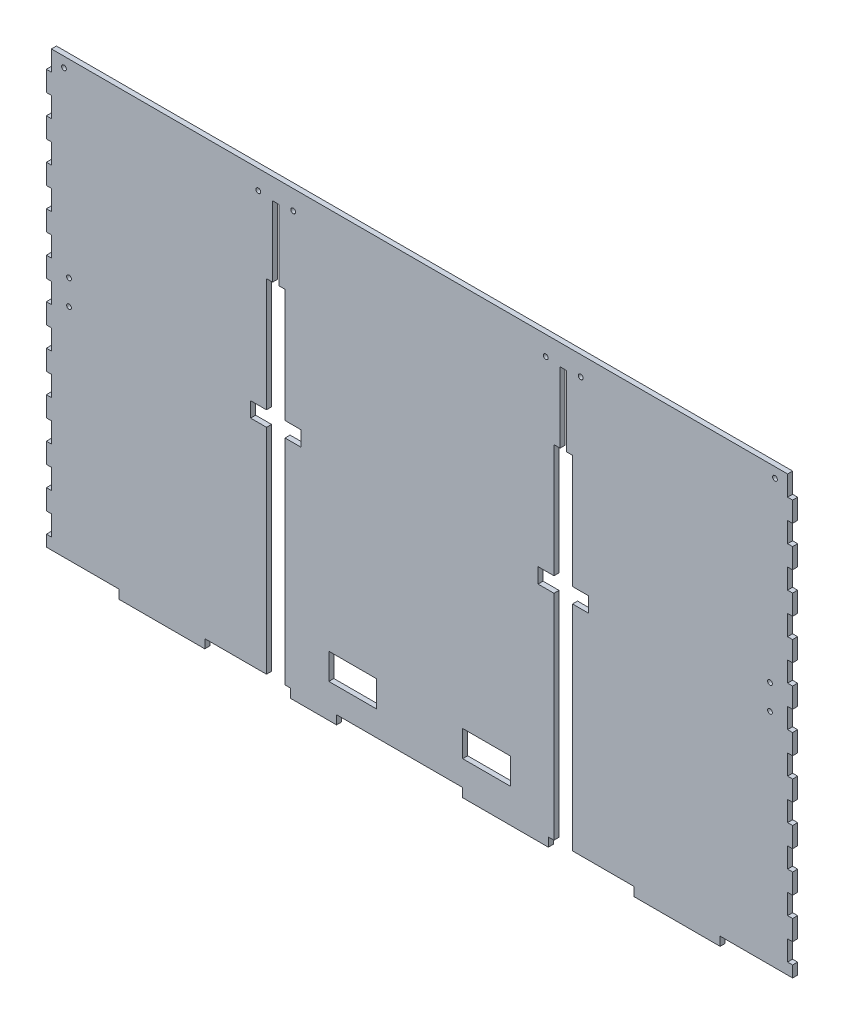
SolidWorks part; units mm, degrees
other "Markup1"
sketch "Sketch18" plane through (-235.3945, -139.7, 3.175) normal (0, 0, 1) x (1, 0, 0)
material "Acrylic (Medium-high impact)"
ref_plane "Front Plane" through (0, 0, 0) normal (0, 0, 1) x (1, 0, 0)
ref_plane "Top Plane" through (0, 0, 0) normal (0, 1, 0) x (1, 0, 0)
ref_plane "Right Plane" through (0, 0, 0) normal (1, 0, 0) x (0, 0, -1)
sketch "Sketch1" plane through (0, 0, 0) normal (0, 0, 1) x (1, 0, 0)
  line L0 (0, 139.7) -> (0, -139.7) construction
  line L1 (-406.4, 139.7) -> (406.4, 139.7)
  line L2 (-406.4, 139.7) -> (-406.4, -139.7)
  line L3 (-406.4, -139.7) -> (406.4, -139.7)
  line L4 (406.4, 139.7) -> (406.4, -139.7)
  line L49 (-381, 127) -> (-381, 114.3)
  line L54 (-381, 139.7) -> (-377.825, 139.7)
  line L55 (-381, 139.7) -> (-381, 127)
  line L56 (-381, 127) -> (-377.825, 127)
  line L57 (-377.825, 139.7) -> (-377.825, 127)
  line L58 (-381, 127) -> (-377.825, 127)
  line L59 (-377.825, 127) -> (-377.825, 114.3)
  line L60 (-381, 114.3) -> (-377.825, 114.3)
  line L61 (-381, 114.3) -> (-381, 101.6)
  line L62 (-381, 114.3) -> (-377.825, 114.3)
  line L63 (-377.825, 114.3) -> (-377.825, 101.6)
  line L64 (-381, 101.6) -> (-377.825, 101.6)
  line L65 (-381, 101.6) -> (-381, 88.9)
  line L66 (-381, 101.6) -> (-377.825, 101.6)
  line L67 (-377.825, 101.6) -> (-377.825, 88.9)
  line L68 (-381, 88.9) -> (-377.825, 88.9)
  line L69 (-381, 88.9) -> (-381, 76.2)
  line L70 (-381, 88.9) -> (-377.825, 88.9)
  line L71 (-377.825, 88.9) -> (-377.825, 76.2)
  line L72 (-381, 76.2) -> (-377.825, 76.2)
  line L73 (-381, 76.2) -> (-381, 63.5)
  line L74 (-381, 76.2) -> (-377.825, 76.2)
  line L75 (-377.825, 76.2) -> (-377.825, 63.5)
  line L76 (-381, 63.5) -> (-377.825, 63.5)
  line L77 (-381, 63.5) -> (-381, 50.8)
  line L78 (-381, 63.5) -> (-377.825, 63.5)
  line L79 (-377.825, 63.5) -> (-377.825, 50.8)
  line L80 (-381, 50.8) -> (-377.825, 50.8)
  line L81 (-381, 50.8) -> (-381, 38.1)
  line L82 (-381, 50.8) -> (-377.825, 50.8)
  line L83 (-377.825, 50.8) -> (-377.825, 38.1)
  line L84 (-381, 38.1) -> (-377.825, 38.1)
  line L85 (-381, 38.1) -> (-381, 25.4)
  line L86 (-381, 38.1) -> (-377.825, 38.1)
  line L87 (-377.825, 38.1) -> (-377.825, 25.4)
  line L88 (-381, 25.4) -> (-377.825, 25.4)
  line L89 (377.825, 127) -> (377.825, 114.3)
  line L90 (377.825, 139.7) -> (381, 139.7)
  line L91 (377.825, 139.7) -> (377.825, 127)
  line L92 (377.825, 127) -> (381, 127)
  line L93 (381, 139.7) -> (381, 127)
  line L94 (377.825, 127) -> (381, 127)
  line L95 (381, 127) -> (381, 114.3)
  line L96 (377.825, 114.3) -> (381, 114.3)
  line L97 (377.825, 114.3) -> (377.825, 101.6)
  line L98 (377.825, 114.3) -> (381, 114.3)
  line L99 (381, 114.3) -> (381, 101.6)
  line L100 (377.825, 101.6) -> (381, 101.6)
  line L101 (377.825, 101.6) -> (377.825, 88.9)
  line L102 (377.825, 101.6) -> (381, 101.6)
  line L103 (381, 101.6) -> (381, 88.9)
  line L104 (377.825, 88.9) -> (381, 88.9)
  line L105 (377.825, 88.9) -> (377.825, 76.2)
  line L106 (377.825, 88.9) -> (381, 88.9)
  line L107 (381, 88.9) -> (381, 76.2)
  line L108 (377.825, 76.2) -> (381, 76.2)
  line L109 (377.825, 76.2) -> (377.825, 63.5)
  line L110 (377.825, 76.2) -> (381, 76.2)
  line L111 (381, 76.2) -> (381, 63.5)
  line L112 (377.825, 63.5) -> (381, 63.5)
  line L113 (377.825, 63.5) -> (377.825, 50.8)
  line L114 (377.825, 63.5) -> (381, 63.5)
  line L115 (381, 63.5) -> (381, 50.8)
  line L116 (377.825, 50.8) -> (381, 50.8)
  line L117 (377.825, 50.8) -> (377.825, 38.1)
  line L118 (377.825, 50.8) -> (381, 50.8)
  line L119 (381, 50.8) -> (381, 38.1)
  line L120 (377.825, 38.1) -> (381, 38.1)
  line L121 (377.825, 38.1) -> (377.825, 25.4)
  line L122 (377.825, 38.1) -> (381, 38.1)
  line L123 (381, 38.1) -> (381, 25.4)
  line L124 (377.825, 25.4) -> (381, 25.4)
  line L125 (-352.2133, -134.112) -> (-352.2133, -139.7)
  line L126 (-406.4, -134.112) -> (-352.2133, -134.112)
  line L127 (-406.4, -134.112) -> (-406.4, -139.7)
  line L128 (-406.4, -139.7) -> (-352.2133, -139.7)
  line L129 (-352.2133, -134.112) -> (-352.2133, -139.7)
  line L130 (-352.2133, -134.112) -> (-298.0267, -134.112)
  line L131 (-298.0267, -134.112) -> (-298.0267, -139.7)
  line L132 (-352.2133, -139.7) -> (-298.0267, -139.7)
  line L133 (-298.0267, -134.112) -> (-298.0267, -139.7)
  line L134 (-298.0267, -134.112) -> (-243.84, -134.112)
  line L135 (-243.84, -134.112) -> (-243.84, -139.7)
  line L136 (-298.0267, -139.7) -> (-243.84, -139.7)
  line L137 (-243.84, -134.112) -> (-243.84, -139.7)
  line L138 (-243.84, -134.112) -> (-189.6533, -134.112)
  line L139 (-189.6533, -134.112) -> (-189.6533, -139.7)
  line L140 (-243.84, -139.7) -> (-189.6533, -139.7)
  line L141 (-189.6533, -134.112) -> (-189.6533, -139.7)
  line L142 (-189.6533, -134.112) -> (-135.4667, -134.112)
  line L143 (-135.4667, -134.112) -> (-135.4667, -139.7)
  line L144 (-189.6533, -139.7) -> (-135.4667, -139.7)
  line L145 (-135.4667, -134.112) -> (-135.4667, -139.7)
  line L146 (-135.4667, -134.112) -> (-81.28, -134.112)
  line L147 (-81.28, -134.112) -> (-81.28, -139.7)
  line L148 (-135.4667, -139.7) -> (-81.28, -139.7)
  line L149 (-81.28, -134.112) -> (-81.28, -139.7)
  line L150 (-81.28, -134.112) -> (-27.0933, -134.112)
  line L151 (-27.0933, -134.112) -> (-27.0933, -139.7)
  line L152 (-81.28, -139.7) -> (-27.0933, -139.7)
  line L153 (-27.0933, -134.112) -> (-27.0933, -139.7)
  line L154 (-27.0933, -134.112) -> (27.0933, -134.112)
  line L155 (27.0933, -134.112) -> (27.0933, -139.7)
  line L156 (-27.0933, -139.7) -> (27.0933, -139.7)
  line L157 (27.0933, -134.112) -> (27.0933, -139.7)
  line L158 (27.0933, -134.112) -> (81.28, -134.112)
  line L159 (81.28, -134.112) -> (81.28, -139.7)
  line L160 (27.0933, -139.7) -> (81.28, -139.7)
  line L161 (81.28, -134.112) -> (81.28, -139.7)
  line L162 (81.28, -134.112) -> (135.4667, -134.112)
  line L163 (135.4667, -134.112) -> (135.4667, -139.7)
  line L164 (81.28, -139.7) -> (135.4667, -139.7)
  line L165 (135.4667, -134.112) -> (135.4667, -139.7)
  line L166 (135.4667, -134.112) -> (189.6533, -134.112)
  line L167 (189.6533, -134.112) -> (189.6533, -139.7)
  line L168 (135.4667, -139.7) -> (189.6533, -139.7)
  line L169 (189.6533, -134.112) -> (189.6533, -139.7)
  line L170 (189.6533, -134.112) -> (243.84, -134.112)
  line L171 (243.84, -134.112) -> (243.84, -139.7)
  line L172 (189.6533, -139.7) -> (243.84, -139.7)
  line L173 (243.84, -134.112) -> (243.84, -139.7)
  line L174 (243.84, -134.112) -> (298.0267, -134.112)
  line L175 (298.0267, -134.112) -> (298.0267, -139.7)
  line L176 (243.84, -139.7) -> (298.0267, -139.7)
  line L177 (298.0267, -134.112) -> (298.0267, -139.7)
  line L178 (298.0267, -134.112) -> (352.2133, -134.112)
  line L179 (352.2133, -134.112) -> (352.2133, -139.7)
  line L180 (298.0267, -139.7) -> (352.2133, -139.7)
  line L181 (352.2133, -134.112) -> (352.2133, -139.7)
  line L182 (352.2133, -134.112) -> (406.4, -134.112)
  line L183 (406.4, -134.112) -> (406.4, -139.7)
  line L184 (352.2133, -139.7) -> (406.4, -139.7)
  line L205 (-90.678, 84.5227) -> (-90.678, -139.7) construction
  line L206 (90.678, 84.5227) -> (90.678, -139.7) construction
  line L207 (-90.678, -27.5886) -> (90.678, -27.5886) construction
  line L208 (-381, 25.4) -> (-381, 12.7)
  line L209 (-381, 25.4) -> (-377.825, 25.4)
  line L210 (-377.825, 25.4) -> (-377.825, 12.7)
  line L211 (-381, 12.7) -> (-377.825, 12.7)
  line L212 (-381, 12.7) -> (-381, 0)
  line L213 (-381, 12.7) -> (-377.825, 12.7)
  line L214 (-377.825, 12.7) -> (-377.825, 0)
  line L215 (-381, 0) -> (-377.825, 0)
  line L224 (-377.825, 0) -> (377.825, 0) construction
  line L229 (377.825, 25.4) -> (377.825, 12.7)
  line L230 (377.825, 25.4) -> (381, 25.4)
  line L231 (381, 25.4) -> (381, 12.7)
  line L232 (377.825, 12.7) -> (381, 12.7)
  line L233 (377.825, 12.7) -> (377.825, 0)
  line L234 (377.825, 12.7) -> (381, 12.7)
  line L235 (381, 12.7) -> (381, 0)
  line L236 (377.825, 0) -> (381, 0)
  line L237 (-381, 0) -> (-381, -12.7)
  line L238 (-381, 0) -> (-377.825, 0)
  line L239 (-377.825, 0) -> (-377.825, -12.7)
  line L240 (-381, -12.7) -> (-377.825, -12.7)
  line L241 (-381, -12.7) -> (-381, -25.4)
  line L242 (-381, -12.7) -> (-377.825, -12.7)
  line L243 (-377.825, -12.7) -> (-377.825, -25.4)
  line L244 (-381, -25.4) -> (-377.825, -25.4)
  line L245 (-381, -25.4) -> (-381, -38.1)
  line L246 (-381, -25.4) -> (-377.825, -25.4)
  line L247 (-377.825, -25.4) -> (-377.825, -38.1)
  line L248 (-381, -38.1) -> (-377.825, -38.1)
  line L249 (-381, -38.1) -> (-381, -50.8)
  line L250 (-381, -38.1) -> (-377.825, -38.1)
  line L251 (-377.825, -38.1) -> (-377.825, -50.8)
  line L252 (-381, -50.8) -> (-377.825, -50.8)
  line L253 (-381, -50.8) -> (-381, -63.5)
  line L254 (-381, -50.8) -> (-377.825, -50.8)
  line L255 (-377.825, -50.8) -> (-377.825, -63.5)
  line L256 (-381, -63.5) -> (-377.825, -63.5)
  line L257 (-381, -63.5) -> (-381, -76.2)
  line L258 (-381, -63.5) -> (-377.825, -63.5)
  line L259 (-377.825, -63.5) -> (-377.825, -76.2)
  line L260 (-381, -76.2) -> (-377.825, -76.2)
  line L261 (-381, -76.2) -> (-381, -88.9)
  line L262 (-381, -76.2) -> (-377.825, -76.2)
  line L263 (-377.825, -76.2) -> (-377.825, -88.9)
  line L264 (-381, -88.9) -> (-377.825, -88.9)
  line L265 (-381, -88.9) -> (-381, -101.6)
  line L266 (-381, -88.9) -> (-377.825, -88.9)
  line L267 (-377.825, -88.9) -> (-377.825, -101.6)
  line L268 (-381, -101.6) -> (-377.825, -101.6)
  line L269 (-381, -101.6) -> (-381, -114.3)
  line L270 (-381, -101.6) -> (-377.825, -101.6)
  line L271 (-377.825, -101.6) -> (-377.825, -114.3)
  line L272 (-381, -114.3) -> (-377.825, -114.3)
  line L273 (-381, -114.3) -> (-381, -127)
  line L274 (-381, -114.3) -> (-377.825, -114.3)
  line L275 (-377.825, -114.3) -> (-377.825, -127)
  line L276 (-381, -127) -> (-377.825, -127)
  line L277 (-381, -127) -> (-381, -139.7)
  line L278 (-381, -127) -> (-377.825, -127)
  line L279 (-377.825, -127) -> (-377.825, -139.7)
  line L280 (-381, -139.7) -> (-377.825, -139.7)
  line L281 (377.825, 0) -> (377.825, -12.7)
  line L282 (377.825, 0) -> (381, 0)
  line L283 (381, 0) -> (381, -12.7)
  line L284 (377.825, -12.7) -> (381, -12.7)
  line L285 (377.825, -12.7) -> (377.825, -25.4)
  line L286 (377.825, -12.7) -> (381, -12.7)
  line L287 (381, -12.7) -> (381, -25.4)
  line L288 (377.825, -25.4) -> (381, -25.4)
  line L289 (377.825, -25.4) -> (377.825, -38.1)
  line L290 (377.825, -25.4) -> (381, -25.4)
  line L291 (381, -25.4) -> (381, -38.1)
  line L292 (377.825, -38.1) -> (381, -38.1)
  line L293 (377.825, -38.1) -> (377.825, -50.8)
  line L294 (377.825, -38.1) -> (381, -38.1)
  line L295 (381, -38.1) -> (381, -50.8)
  line L296 (377.825, -50.8) -> (381, -50.8)
  line L297 (377.825, -50.8) -> (377.825, -63.5)
  line L298 (377.825, -50.8) -> (381, -50.8)
  line L299 (381, -50.8) -> (381, -63.5)
  line L300 (377.825, -63.5) -> (381, -63.5)
  line L301 (377.825, -63.5) -> (377.825, -76.2)
  line L302 (377.825, -63.5) -> (381, -63.5)
  line L303 (381, -63.5) -> (381, -76.2)
  line L304 (377.825, -76.2) -> (381, -76.2)
  line L305 (377.825, -76.2) -> (377.825, -88.9)
  line L306 (377.825, -76.2) -> (381, -76.2)
  line L307 (381, -76.2) -> (381, -88.9)
  line L308 (377.825, -88.9) -> (381, -88.9)
  line L309 (377.825, -88.9) -> (377.825, -101.6)
  line L310 (377.825, -88.9) -> (381, -88.9)
  line L311 (381, -88.9) -> (381, -101.6)
  line L312 (377.825, -101.6) -> (381, -101.6)
  line L313 (377.825, -101.6) -> (377.825, -114.3)
  line L314 (377.825, -101.6) -> (381, -101.6)
  line L315 (381, -101.6) -> (381, -114.3)
  line L316 (377.825, -114.3) -> (381, -114.3)
  line L317 (377.825, -114.3) -> (377.825, -127)
  line L318 (377.825, -114.3) -> (381, -114.3)
  line L319 (381, -114.3) -> (381, -127)
  line L320 (377.825, -127) -> (381, -127)
  line L321 (377.825, -127) -> (377.825, -139.7)
  line L322 (377.825, -127) -> (381, -127)
  line L323 (381, -127) -> (381, -139.7)
  line L324 (377.825, -139.7) -> (381, -139.7)
  point P6 (0, 0)
  point P128 (0, -27.5886)
  point P153 (0, 0)
  dimension "D4" = 12.7
  dimension "D5" = 3.175
  dimension "D10" = 181.356
  dimension "D12" = 755.65
  dimension "D8" = 812.8
  dimension "D11" = 54.1867
  dimension "D2" = 273.812
  dimension "D9" = 279.4
  dimension "D3" = 22
  dimension "D7" = 15
  dimension "D6" = 22
extrude "Main Extrude" add sketch "Sketch1" along normal blind 3.175 contours L321 L317 L313 L309 L305 L301 L297 L293 L289 L285 L281 L233 L229 L121 L117 L113 L109 L105 L101 L97 L89 L91 L1 L57 L59 L63 L67 L71 L75 L79 L83 L87 L210 L214 L239 L243 L247 L251 L255 L259 L263 L267 L271 L275 L279 L126 L130 L134 L138 L142 L146 | L277 L273 L269 L265 L261 L257 L253 L249 L245 L241 L237 L212 L208 L85 L81 L77 L73 L69 L65 L61 L49 L55 L1 L2 L126 | L319 L323 L182 L4 L1 L93 L95 L99 L103 L107 L111 L115 L119 L123 L231 L235 L283 L287 L291 L295 L299 L303 L307 L311 L315 | L126 L279 L3 L125 | L135 L134 L131 L3 | L143 L142 L139 L3 | L151 L150 L147 L3 | L159 L158 L155 L3 | L167 L166 L163 L3 | L175 L174 L171 L3 | L323 L182 L321 L184 | L89 L96 L95 L92 | L101 L104 L103 L100 | L109 L112 L111 L108 | L117 L120 L119 L116 | L229 L232 L231 L124 | L281 L284 L283 L236 | L289 L292 L291 L288 | L297 L300 L299 L296 | L305 L308 L307 L304 | L313 L316 L315 L312 | L323 L320 L321 L182 | L49 L60 L59 L56 | L65 L68 L67 L64 | L73 L76 L75 L72 | L81 L84 L83 L80 | L208 L211 L210 L88 | L237 L240 L239 L215 | L245 L248 L247 L244 | L253 L256 L255 L252 | L261 L264 L263 L260 | L269 L272 L271 L268 | L279 L276 L277 L126 | L277 L126 L2 L3 | L321 L182 L179 L3 | L182 L323 L3 L4 | L279 L126 L277 L128 region at (-393.7, 2.794, 0) region at (-393.7, -136.906, 0) region at (0, 2.794, 0) region at (-379.4125, 120.65, 0) region at (-379.4125, -130.556, 0) region at (-379.4125, -136.906, 0) region at (-365.0192, -136.906, 0) region at (393.7, 2.794, 0) region at (379.4125, 120.65, 0) region at (-379.4125, 95.25, 0) region at (-379.4125, -107.95, 0) region at (-270.9333, -136.906, 0) region at (393.7, -136.906, 0) region at (379.4125, 95.25, 0) region at (-379.4125, 69.85, 0) region at (-379.4125, -82.55, 0) region at (379.4125, -136.906, 0) region at (379.4125, -130.556, 0) region at (-162.56, -136.906, 0) region at (365.0192, -136.906, 0) region at (379.4125, 69.85, 0) region at (-379.4125, 44.45, 0) region at (-379.4125, -57.15, 0) region at (379.4125, -107.95, 0) region at (-54.1867, -136.906, 0) region at (270.9333, -136.906, 0) region at (379.4125, 44.45, 0) region at (-379.4125, 19.05, 0) region at (-379.4125, -31.75, 0) region at (379.4125, -82.55, 0) region at (54.1867, -136.906, 0) region at (162.56, -136.906, 0) region at (379.4125, 19.05, 0) region at (-379.4125, -6.35, 0) region at (379.4125, -57.15, 0) region at (379.4125, -6.35, 0) region at (379.4125, -31.75, 0)
sketch "Sketch8" plane through (0, 0, 3.175) normal (0, 0, 1) x (1, 0, 0)
  line L0 (-406.4, 139.7) -> (-406.4, -139.7) construction
  line L1 (-381, 28.2575) -> (-384.175, 28.2575)
  line L2 (-381, 28.2575) -> (-381, -3.6195)
  line L3 (-381, -3.6195) -> (-384.175, -3.6195)
  line L4 (-384.175, 28.2575) -> (-384.175, -3.6195)
  line L5 (-406.4, -139.7) -> (-352.2133, -139.7) construction
  line L6 (381, 28.2575) -> (384.175, 28.2575)
  line L7 (381, 28.2575) -> (381, -3.6195)
  line L8 (381, -3.6195) -> (384.175, -3.6195)
  line L9 (384.175, 28.2575) -> (384.175, -3.6195)
  line L11 (-381, 88.9) -> (-381, 76.2) construction
  line L12 (-352.2133, -134.112) -> (-298.0267, -134.112) construction
  line L13 (381, 88.9) -> (381, 76.2) construction
  line L14 (-393.7, -120.65) -> (393.7, -120.65) construction
  circle A0 centre (-393.7, -120.65) radius 1.5
  circle A1 centre (393.7, -120.65) radius 1.5
  point P6 (0, -120.65)
  point P16 (-384.175, 12.319)
  dimension "D5" = 3
  dimension "D1" = 31.877
  dimension "D2" = 3.175
  dimension "D3" = 146.431
  dimension "D4" = 19.05
  dimension "D6" = 12.7
extrude "Mount Holes" cut sketch "Sketch8" against normal through all
sketch "Sketch3" plane through (0, 0, 3.175) normal (0, 0, 1) x (1, 0, 0)
  line L0 (-135.4667, -134.112) -> (-81.28, -134.112) construction
  line L1 (-96.52, 126.492) -> (-84.836, 126.492)
  line L2 (-96.52, 126.492) -> (-96.52, -134.112)
  line L3 (-96.52, -134.112) -> (-84.836, -134.112)
  line L4 (-84.836, 126.492) -> (-84.836, -134.112)
  line L5 (81.28, -134.112) -> (135.4667, -134.112) construction
  line L6 (84.836, 126.492) -> (96.52, 126.492)
  line L7 (84.836, 126.492) -> (84.836, -134.112)
  line L8 (84.836, -134.112) -> (96.52, -134.112)
  line L9 (96.52, 126.492) -> (96.52, -134.112)
  line L10 (-84.836, -3.81) -> (84.836, -3.81) construction
  line L12 (-106.553, 10.3505) -> (-74.803, 10.3505)
  line L13 (-106.553, 10.3505) -> (-106.553, 0.8255)
  line L14 (-106.553, 0.8255) -> (-74.803, 0.8255)
  line L15 (-74.803, 10.3505) -> (-74.803, 0.8255)
  line L16 (74.803, 10.3505) -> (106.553, 10.3505)
  line L17 (74.803, 10.3505) -> (74.803, 0.8255)
  line L18 (74.803, 0.8255) -> (106.553, 0.8255)
  line L19 (106.553, 10.3505) -> (106.553, 0.8255)
  line L20 (-96.52, 126.492) -> (-92.6465, 126.492)
  line L21 (-96.52, 126.492) -> (-96.52, 82.042)
  line L22 (-96.52, 82.042) -> (-92.6465, 82.042)
  line L23 (-92.6465, 126.492) -> (-92.6465, 82.042)
  line L24 (-84.836, 126.492) -> (-88.7095, 126.492)
  line L25 (-84.836, 126.492) -> (-84.836, 82.042)
  line L26 (-84.836, 82.042) -> (-88.7095, 82.042)
  line L27 (-88.7095, 126.492) -> (-88.7095, 82.042)
  line L28 (84.836, 126.492) -> (88.7095, 126.492)
  line L29 (84.836, 126.492) -> (84.836, 82.042)
  line L30 (84.836, 82.042) -> (88.7095, 82.042)
  line L31 (88.7095, 126.492) -> (88.7095, 82.042)
  line L32 (96.52, 126.492) -> (92.6465, 126.492)
  line L33 (96.52, 126.492) -> (96.52, 82.042)
  line L34 (96.52, 82.042) -> (92.6465, 82.042)
  line L35 (92.6465, 126.492) -> (92.6465, 82.042)
  point P14 (-90.678, 126.492)
  point P15 (90.678, 126.492)
  point P16 (0, -3.81)
  point P27 (-90.678, 10.3505)
  point P28 (90.678, 10.3505)
  point P29 (-74.803, 5.588)
  dimension "D1" = 11.684
  dimension "D2" = 260.604
  dimension "D3" = 181.356
  dimension "D4" = 9.525
  dimension "D5" = 139.7
  dimension "D6" = 31.75
  dimension "D8" = 3.937
  dimension "D7" = 44.45
extrude "Door Slots" cut sketch "Sketch3" against normal through all contours L2 L12 L4 L1 | L2 L14 L4 L12 | L15 L12 L4 L14 | L13 L14 L2 L12 | L14 L2 L3 L4 | L7 L16 L9 L6 | L7 L18 L9 L16 | L19 L16 L9 L18 | L17 L18 L7 L16 | L18 L7 L8 L9 region at (-90.678, 56.2317, 3.175) region at (-90.678, 5.588, 3.175) region at (-101.5365, 5.588, 3.175) region at (-90.678, -66.6433, 3.175) region at (-79.8195, 5.588, 3.175) region at (90.678, 56.2317, 3.175) region at (90.678, 5.588, 3.175) region at (79.8195, 5.588, 3.175) region at (90.678, -66.6432, 3.175) region at (101.5365, 5.588, 3.175)
sketch "Sketch4" plane through (0, 0, 0) normal (0, 0, 1) x (1, 0, 0)
  line L1 (-81.28, -139.7) -> (-27.0933, -139.7) construction
  line L2 (-55.48, -112.41) -> (-52.178, -112.41)
  line L3 (-52.178, -112.41) -> (-52.178, -101.792)
  line L4 (-52.178, -101.792) -> (-2.178, -101.792)
  line L5 (-2.178, -101.792) -> (-2.178, -112.41)
  line L6 (-2.178, -112.41) -> (1.124, -112.41)
  line L9 (-55.48, -112.41) -> (-55.48, -134.112)
  line L10 (-55.48, -134.112) -> (-52.178, -134.112)
  line L11 (-52.178, -134.112) -> (-52.178, -139.7)
  line L12 (1.124, -112.41) -> (1.124, -134.112)
  line L13 (1.124, -134.112) -> (-2.178, -134.112)
  line L14 (-2.178, -134.112) -> (-2.178, -139.7)
  line L15 (-52.178, -139.7) -> (-2.178, -139.7)
  line L16 (-27.0933, -134.112) -> (27.0933, -134.112) construction
  line L18 (12.128, -101.792) -> (42.228, -101.792)
  line L19 (12.128, -101.792) -> (12.128, -118.491)
  line L20 (12.128, -118.491) -> (42.228, -118.491)
  line L21 (42.228, -101.792) -> (42.228, -118.491)
  line L22 (-27.0933, -134.112) -> (27.0933, -134.112) construction
  line L24 (-96.52, -134.112) -> (-84.836, -134.112) construction
  line L25 (84.836, -134.112) -> (96.52, -134.112) construction
  point P9 (-27.178, -101.792)
  point P10 (-27.178, -139.7)
  point P22 (27.178, -118.491)
  point P25 (90.678, -134.112)
  point P30 (-90.678, -134.112)
  dimension "D1" = 50
  dimension "D2" = 3.302
  dimension "D4" = 21.702
  dimension "D5" = 30.1
  dimension "D9" = 63.5
  dimension "D8" = 63.5
  dimension "D3" = 32.32
  dimension "D7" = 15.621
  dimension "D6" = 32.32
extrude "Trough and Lever Holes" [suppressed] cut sketch "Sketch4" along normal through all contours L11 L15 L14 L13 L12 L6 L5 L4 L3 L2 L9 L10 | L21 L18 L19 L20
sketch "Sketch5" plane through (0, 0, 3.175) normal (0, 0, 1) x (1, 0, 0)
  line L0 (-90.678, 126.492) -> (-90.678, -134.112) construction
  line L1 (-96.52, 126.492) -> (-84.836, 126.492) construction
  line L2 (-96.52, -134.112) -> (-84.836, -134.112) construction
  line L3 (90.678, 126.492) -> (90.678, -134.112) construction
  line L4 (84.836, 126.492) -> (96.52, 126.492) construction
  line L5 (84.836, -134.112) -> (96.52, -134.112) construction
  line L6 (-135.4667, -134.112) -> (-96.52, -134.112) construction
  line L19 (-99.998, -134.112) -> (-96.3199, -134.112)
  line L20 (-99.998, -134.112) -> (-99.998, -108.712)
  line L21 (-99.998, -108.712) -> (-96.3199, -108.712)
  line L22 (-96.3199, -134.112) -> (-96.3199, -108.712)
  line L24 (-99.998, -108.712) -> (-96.3199, -108.712)
  line L25 (-99.998, -108.712) -> (-99.998, -83.312)
  line L26 (-99.998, -83.312) -> (-96.3199, -83.312)
  line L27 (-96.3199, -108.712) -> (-96.3199, -83.312)
  line L28 (-96.3199, -83.312) -> (-99.998, -83.312)
  line L29 (-96.3199, -83.312) -> (-96.3199, -57.912)
  line L30 (-96.3199, -57.912) -> (-99.998, -57.912)
  line L31 (-99.998, -83.312) -> (-99.998, -57.912)
  line L32 (-99.998, -57.912) -> (-96.3199, -57.912)
  line L33 (-99.998, -57.912) -> (-99.998, -32.512)
  line L34 (-99.998, -32.512) -> (-96.3199, -32.512)
  line L35 (-96.3199, -57.912) -> (-96.3199, -32.512)
  line L36 (-96.3199, -32.512) -> (-99.998, -32.512)
  line L37 (-96.3199, -32.512) -> (-96.3199, -7.112)
  line L38 (-96.3199, -7.112) -> (-99.998, -7.112)
  line L39 (-99.998, -32.512) -> (-99.998, -7.112)
  line L40 (-81.358, -108.712) -> (-85.0361, -108.712)
  line L41 (-85.0361, -134.112) -> (-85.0361, -108.712)
  line L42 (-81.358, -134.112) -> (-85.0361, -134.112)
  line L43 (-81.358, -134.112) -> (-81.358, -108.712)
  line L44 (-81.358, -83.312) -> (-85.0361, -83.312)
  line L45 (-85.0361, -108.712) -> (-85.0361, -83.312)
  line L46 (-81.358, -108.712) -> (-85.0361, -108.712)
  line L47 (-81.358, -108.712) -> (-81.358, -83.312)
  line L48 (-85.0361, -57.912) -> (-81.358, -57.912)
  line L49 (-81.358, -83.312) -> (-81.358, -57.912)
  line L50 (-85.0361, -83.312) -> (-81.358, -83.312)
  line L51 (-85.0361, -83.312) -> (-85.0361, -57.912)
  line L52 (-81.358, -32.512) -> (-85.0361, -32.512)
  line L53 (-85.0361, -57.912) -> (-85.0361, -32.512)
  line L54 (-81.358, -57.912) -> (-85.0361, -57.912)
  line L55 (-81.358, -57.912) -> (-81.358, -32.512)
  line L56 (-85.0361, -7.112) -> (-81.358, -7.112)
  line L57 (-81.358, -32.512) -> (-81.358, -7.112)
  line L58 (-85.0361, -32.512) -> (-81.358, -32.512)
  line L59 (-85.0361, -32.512) -> (-85.0361, -7.112)
  line L60 (0, -1.7463) -> (0, 1.7463) construction
  line L61 (99.998, -108.712) -> (96.3199, -108.712)
  line L62 (96.3199, -134.112) -> (96.3199, -108.712)
  line L63 (99.998, -134.112) -> (96.3199, -134.112)
  line L64 (99.998, -134.112) -> (99.998, -108.712)
  line L65 (99.998, -83.312) -> (96.3199, -83.312)
  line L66 (96.3199, -108.712) -> (96.3199, -83.312)
  line L67 (99.998, -108.712) -> (96.3199, -108.712)
  line L68 (99.998, -108.712) -> (99.998, -83.312)
  line L69 (96.3199, -57.912) -> (99.998, -57.912)
  line L70 (99.998, -83.312) -> (99.998, -57.912)
  line L71 (96.3199, -83.312) -> (99.998, -83.312)
  line L72 (96.3199, -83.312) -> (96.3199, -57.912)
  line L73 (99.998, -32.512) -> (96.3199, -32.512)
  line L74 (96.3199, -57.912) -> (96.3199, -32.512)
  line L75 (99.998, -57.912) -> (96.3199, -57.912)
  line L76 (99.998, -57.912) -> (99.998, -32.512)
  line L77 (96.3199, -7.112) -> (99.998, -7.112)
  line L78 (99.998, -32.512) -> (99.998, -7.112)
  line L79 (96.3199, -32.512) -> (99.998, -32.512)
  line L80 (96.3199, -32.512) -> (96.3199, -7.112)
  line L81 (85.0361, -32.512) -> (85.0361, -7.112)
  line L82 (85.0361, -32.512) -> (81.358, -32.512)
  line L83 (81.358, -32.512) -> (81.358, -7.112)
  line L84 (85.0361, -7.112) -> (81.358, -7.112)
  line L85 (81.358, -57.912) -> (81.358, -32.512)
  line L86 (81.358, -57.912) -> (85.0361, -57.912)
  line L87 (85.0361, -57.912) -> (85.0361, -32.512)
  line L88 (81.358, -32.512) -> (85.0361, -32.512)
  line L89 (85.0361, -83.312) -> (85.0361, -57.912)
  line L90 (85.0361, -83.312) -> (81.358, -83.312)
  line L91 (81.358, -83.312) -> (81.358, -57.912)
  line L92 (85.0361, -57.912) -> (81.358, -57.912)
  line L93 (81.358, -108.712) -> (81.358, -83.312)
  line L94 (81.358, -108.712) -> (85.0361, -108.712)
  line L95 (85.0361, -108.712) -> (85.0361, -83.312)
  line L96 (81.358, -83.312) -> (85.0361, -83.312)
  line L97 (81.358, -134.112) -> (81.358, -108.712)
  line L98 (81.358, -134.112) -> (85.0361, -134.112)
  line L99 (85.0361, -134.112) -> (85.0361, -108.712)
  line L100 (81.358, -108.712) -> (85.0361, -108.712)
  dimension "D1" = 25.4
  dimension "D3" = 5.6419
  dimension "D2" = 9.32
extrude "Door Guide Slots" [suppressed] cut sketch "Sketch5" against normal through all contours L21 L27 L26 L25 | L30 L35 L34 L33 | L48 L55 L52 L53 | L40 L47 L44 L45 | L86 L87 L82 L85 | L94 L95 L90 L93 | L69 L76 L73 L74 | L61 L68 L65 L66
sketch "Sketch7" plane through (0, 0, 3.175) normal (0, 0, 1) x (1, 0, 0)
  line L0 (-25.908, -109.9715) -> (25.908, -109.9715) construction
  line L1 (-56.008, -105.601) -> (-25.908, -105.601)
  line L2 (-56.008, -105.601) -> (-56.008, -114.342)
  line L3 (-56.008, -114.342) -> (-25.908, -114.342)
  line L4 (-25.908, -105.601) -> (-25.908, -114.342)
  line L5 (56.008, -105.601) -> (25.908, -105.601)
  line L6 (56.008, -105.601) -> (56.008, -114.342)
  line L7 (56.008, -114.342) -> (25.908, -114.342)
  line L8 (25.908, -105.601) -> (25.908, -114.342)
  line L9 (0, -109.9715) -> (0, 0) construction
  line L10 (-135.4667, -134.112) -> (-96.52, -134.112) construction
  line L11 (-27.0933, -134.112) -> (27.0933, -134.112) construction
  dimension "D1" = 28.511
  dimension "D2" = 30.1
  dimension "D3" = 51.816
  dimension "D4" = 19.77
extrude "Lever Holes" [suppressed] cut sketch "Sketch7" against normal through all
sketch "Sketch10" plane through (0, 0, 3.175) normal (0, 0, 1) x (1, 0, 0)
  line L0 (-101.678, 127.492) -> (-79.678, 127.492) construction
  line L2 (-92.6465, 126.492) -> (-88.7095, 126.492) construction
  line L3 (-90.678, 127.492) -> (-90.678, 126.492) construction
  line L4 (79.678, 127.492) -> (101.678, 127.492) construction
  line L5 (90.678, 127.492) -> (90.678, 126.492) construction
  line L6 (88.7095, 126.492) -> (92.6465, 126.492) construction
  circle A0 centre (-101.678, 127.492) radius 1.5
  circle A1 centre (-79.678, 127.492) radius 1.5
  circle A2 centre (79.678, 127.492) radius 1.5
  circle A3 centre (101.678, 127.492) radius 1.5
  dimension "D1" = 3
  dimension "D2" = 22
  dimension "D3" = 1
extrude "Door Guide Mount Holes" cut sketch "Sketch10" against normal through all
sketch "Sketch12" plane through (0, 0, 3.175) normal (0, 0, 1) x (1, 0, 0)
  line L0 (-246.507, 20.193) -> (-246.507, 4.445) construction
  line L1 (-221.107, 20.193) -> (-221.107, 4.445) construction
  line L2 (-246.507, 20.193) -> (-221.107, 20.193) construction
  line L3 (-246.507, 4.445) -> (-221.107, 4.445) construction
  line L4 (-243.332, 133.35) -> (-224.282, 133.35) construction
  line L5 (-406.4, 139.7) -> (406.4, 139.7) construction
  line L6 (-233.807, 20.193) -> (-233.807, 133.35) construction
  line L7 (-243.84, -134.112) -> (-189.6533, -134.112) construction
  line L8 (0, -1.7463) -> (0, 1.7463) construction
  line L9 (233.807, 20.193) -> (233.807, 133.35) construction
  line L10 (243.332, 133.35) -> (224.282, 133.35) construction
  line L11 (246.507, 4.445) -> (221.107, 4.445) construction
  line L12 (246.507, 20.193) -> (221.107, 20.193) construction
  line L13 (221.107, 20.193) -> (221.107, 4.445) construction
  line L14 (246.507, 20.193) -> (246.507, 4.445) construction
  circle A0 centre (-246.507, 20.193) radius 1.5
  circle A1 centre (-246.507, 4.445) radius 1.5
  circle A2 centre (-221.107, 4.445) radius 1.5
  circle A3 centre (-221.107, 20.193) radius 1.5
  circle A4 centre (-243.332, 133.35) radius 1.5
  circle A5 centre (-224.282, 133.35) radius 1.5
  circle A6 centre (224.282, 133.35) radius 1.5
  circle A7 centre (243.332, 133.35) radius 1.5
  circle A8 centre (221.107, 20.193) radius 1.5
  circle A9 centre (221.107, 4.445) radius 1.5
  circle A10 centre (246.507, 4.445) radius 1.5
  circle A11 centre (246.507, 20.193) radius 1.5
  point P12 (-233.807, 133.35)
  dimension "D1" = 3
  dimension "D2" = 233.807
  dimension "D3" = 19.05
  dimension "D4" = 6.35
  dimension "D5" = 25.4
  dimension "D6" = 15.748
  dimension "D7" = 138.557
extrude "Extension Clip Holes" cut sketch "Sketch12" against normal through all
sketch "Sketch11" plane through (0, 0, 3.175) normal (0, 0, 1) x (1, 0, 0)
  line L0 (-232.2195, 139.7) -> (-232.2195, 127)
  line L1 (-232.2195, 127) -> (-235.3945, 127)
  line L2 (-235.3945, 127) -> (-235.3945, 114.3)
  line L3 (-235.3945, 114.3) -> (-232.2195, 114.3)
  line L4 (232.2195, 139.7) -> (232.2195, 127)
  line L5 (232.2195, 127) -> (235.3945, 127)
  line L6 (235.3945, 127) -> (235.3945, 114.3)
  line L7 (235.3945, 114.3) -> (232.2195, 114.3)
  line L9 (-381, 127) -> (-377.825, 127) construction
  line L10 (-377.825, 139.7) -> (-377.825, 127) construction
  line L11 (235.3945, 120.65) -> (-235.3945, 120.65) construction
  line L12 (-232.2195, 114.3) -> (-232.2195, 101.6)
  line L13 (-232.2195, 101.6) -> (-235.3945, 101.6)
  line L14 (-235.3945, 101.6) -> (-235.3945, 88.9)
  line L15 (-235.3945, 88.9) -> (-232.2195, 88.9)
  line L16 (232.2195, 114.3) -> (232.2195, 101.6)
  line L17 (232.2195, 101.6) -> (235.3945, 101.6)
  line L18 (235.3945, 101.6) -> (235.3945, 88.9)
  line L19 (235.3945, 88.9) -> (232.2195, 88.9)
  line L20 (-232.2195, 88.9) -> (-232.2195, 76.2)
  line L21 (-232.2195, 76.2) -> (-235.3945, 76.2)
  line L22 (-235.3945, 76.2) -> (-235.3945, 63.5)
  line L23 (-235.3945, 63.5) -> (-232.2195, 63.5)
  line L24 (232.2195, 88.9) -> (232.2195, 76.2)
  line L25 (232.2195, 76.2) -> (235.3945, 76.2)
  line L26 (235.3945, 76.2) -> (235.3945, 63.5)
  line L27 (235.3945, 63.5) -> (232.2195, 63.5)
  line L28 (-232.2195, 63.5) -> (-232.2195, 50.8)
  line L29 (-232.2195, 50.8) -> (-235.3945, 50.8)
  line L30 (-235.3945, 50.8) -> (-235.3945, 38.1)
  line L31 (-235.3945, 38.1) -> (-232.2195, 38.1)
  line L32 (232.2195, 63.5) -> (232.2195, 50.8)
  line L33 (232.2195, 50.8) -> (235.3945, 50.8)
  line L34 (235.3945, 50.8) -> (235.3945, 38.1)
  line L35 (235.3945, 38.1) -> (232.2195, 38.1)
  line L36 (-232.2195, 38.1) -> (-232.2195, 25.4)
  line L37 (-232.2195, 25.4) -> (-235.3945, 25.4)
  line L38 (-235.3945, 25.4) -> (-235.3945, 12.7)
  line L39 (-235.3945, 12.7) -> (-232.2195, 12.7)
  line L40 (232.2195, 38.1) -> (232.2195, 25.4)
  line L41 (232.2195, 25.4) -> (235.3945, 25.4)
  line L42 (235.3945, 25.4) -> (235.3945, 12.7)
  line L43 (235.3945, 12.7) -> (232.2195, 12.7)
  line L44 (-232.2195, 12.7) -> (-232.2195, 0)
  line L45 (-232.2195, 0) -> (-235.3945, 0)
  line L46 (-235.3945, 0) -> (-235.3945, -12.7)
  line L47 (-235.3945, -12.7) -> (-232.2195, -12.7)
  line L48 (232.2195, 12.7) -> (232.2195, 0)
  line L50 (232.2195, 0) -> (235.3945, 0)
  line L52 (235.3945, 0) -> (235.3945, -12.7)
  line L53 (235.3945, -12.7) -> (232.2195, -12.7)
  line L54 (-232.2195, -12.7) -> (-232.2195, -25.4)
  line L55 (-232.2195, -25.4) -> (-235.3945, -25.4)
  line L56 (-235.3945, -25.4) -> (-235.3945, -38.1)
  line L57 (-235.3945, -38.1) -> (-232.2195, -38.1)
  line L58 (232.2195, -12.7) -> (232.2195, -25.4)
  line L59 (232.2195, -25.4) -> (235.3945, -25.4)
  line L60 (235.3945, -25.4) -> (235.3945, -38.1)
  line L61 (235.3945, -38.1) -> (232.2195, -38.1)
  line L62 (-232.2195, -38.1) -> (-232.2195, -50.8)
  line L63 (-232.2195, -50.8) -> (-235.3945, -50.8)
  line L64 (-235.3945, -50.8) -> (-235.3945, -63.5)
  line L65 (-235.3945, -63.5) -> (-232.2195, -63.5)
  line L66 (232.2195, -38.1) -> (232.2195, -50.8)
  line L67 (232.2195, -50.8) -> (235.3945, -50.8)
  line L68 (235.3945, -50.8) -> (235.3945, -63.5)
  line L69 (235.3945, -63.5) -> (232.2195, -63.5)
  line L70 (-232.2195, -63.5) -> (-232.2195, -76.2)
  line L71 (-232.2195, -76.2) -> (-235.3945, -76.2)
  line L72 (-235.3945, -76.2) -> (-235.3945, -88.9)
  line L73 (-235.3945, -88.9) -> (-232.2195, -88.9)
  line L74 (232.2195, -63.5) -> (232.2195, -76.2)
  line L75 (232.2195, -76.2) -> (235.3945, -76.2)
  line L76 (235.3945, -76.2) -> (235.3945, -88.9)
  line L77 (235.3945, -88.9) -> (232.2195, -88.9)
  line L78 (-232.2195, -88.9) -> (-232.2195, -101.6)
  line L79 (-232.2195, -101.6) -> (-235.3945, -101.6)
  line L80 (-235.3945, -101.6) -> (-235.3945, -114.3)
  line L81 (-235.3945, -114.3) -> (-232.2195, -114.3)
  line L82 (232.2195, -88.9) -> (232.2195, -101.6)
  line L83 (232.2195, -101.6) -> (235.3945, -101.6)
  line L84 (235.3945, -101.6) -> (235.3945, -114.3)
  line L85 (235.3945, -114.3) -> (232.2195, -114.3)
  line L86 (-232.2195, -114.3) -> (-232.2195, -127)
  line L87 (-232.2195, -127) -> (-235.3945, -127)
  line L88 (-235.3945, -127) -> (-235.3945, -139.7)
  line L90 (232.2195, -114.3) -> (232.2195, -127)
  line L91 (232.2195, -127) -> (235.3945, -127)
  line L92 (235.3945, -127) -> (235.3945, -139.7)
  line L98 (-406.4, 139.7) -> (406.4, 139.7)
  line L99 (-406.4, 139.7) -> (-406.4, -139.7)
  line L100 (-406.4, -139.7) -> (406.4, -139.7)
  line L101 (406.4, 139.7) -> (406.4, -139.7)
  line L102 (-235.3945, -139.7) -> (-232.2195, -139.7)
  line L103 (235.3945, -139.7) -> (232.2195, -139.7)
  point P14 (-233.807, 127)
  point P15 (233.807, 114.3)
  point P18 (0, 120.65)
  dimension "D2" = 11
  dimension "D1" = 467.614
extrude "Extended Side Cut" [suppressed] cut sketch "Sketch11" against normal through all
extrude "Extension Center Cut" cut sketch "Sketch11<3>" against normal through all contours L99 L100 L39 L31 L23 L15 L2 L1 L98 | L101 L98 L80 L77 L76 L75 L72 L69 L68 L67 L64 L61 L60 L59 L56 L53 L52 L50 L100 region at (-320.0962, 0.0584, 3.175) region at (320.0962, 0.0584, 3.175)
sketch "Sketch11<3>" plane through (0, 0, 3.175) normal (0, 0, 1) x (1, 0, 0) same geometry as "Sketch11"
sketch "Sketch14" plane through (0, 0, 3.175) normal (0, 0, 1) x (1, 0, 0)
  line L1 (-232.2195, 139.7) -> (232.2195, 139.7)
  line L2 (-232.2195, 139.7) -> (-232.2195, 165.1)
  line L3 (-232.2195, 165.1) -> (232.2195, 165.1)
  line L4 (232.2195, 139.7) -> (232.2195, 165.1)
  dimension "D1" = 25.4
extrude "Extra Inch" [suppressed] add sketch "Sketch14" against normal up to surface (3.175 mm away)
sketch "Sketch15" [suppressed] plane through (0, 0, 3.175) normal (0, 0, 1) x (1, 0, 0)
  line L1 (-232.2195, 139.7) -> (232.2195, 139.7)
  line L2 (-232.2195, 139.7) -> (-232.2195, 165.1)
  line L3 (-232.2195, 165.1) -> (232.2195, 165.1)
  line L4 (232.2195, 139.7) -> (232.2195, 165.1)
  dimension "D1" = 25.4
extrude "Back Extra Inch" [suppressed] add sketch "Sketch15" against normal up to surface (3.175 mm away)
sketch "Sketch16" [suppressed] plane through (0, 0, 3.175) normal (0, 0, 1) x (1, 0, 0)
  line L1 (-232.2195, 139.7) -> (-406.4, 139.7)
  line L2 (-232.2195, 139.7) -> (-232.2195, 165.1)
  line L3 (-232.2195, 165.1) -> (-406.4, 165.1)
  line L4 (-406.4, 139.7) -> (-406.4, 165.1)
  dimension "D1" = 25.4
extrude "Extended Extra Inch" [suppressed] add sketch "Sketch16" against normal up to surface (3.175 mm away)
sketch "Sketch17" plane through (0, 0, 3.175) normal (0, 0, 1) x (1, 0, 0)
  line L0 (84.836, -134.112) -> (96.52, -134.112) construction
  line L1 (27.241, -101.854) -> (57.341, -101.854)
  line L2 (27.241, -101.854) -> (27.241, -118.364)
  line L3 (27.241, -118.364) -> (57.341, -118.364)
  line L4 (57.341, -101.854) -> (57.341, -118.364)
  line L5 (-57.214, -101.854) -> (-27.114, -101.854)
  line L6 (-57.214, -101.854) -> (-57.214, -118.364)
  line L7 (-57.214, -118.364) -> (-27.114, -118.364)
  line L8 (-27.114, -101.854) -> (-27.114, -118.364)
  line L9 (-96.52, -134.112) -> (-84.836, -134.112) construction
  line L10 (-27.0933, -134.112) -> (27.0933, -134.112) construction
  line L11 (-81.28, -139.7) -> (-27.0933, -139.7) construction
  line L12 (-27.0933, -134.112) -> (-52.324, -134.112)
  line L13 (-27.0933, -134.112) -> (-27.0933, -139.7)
  line L14 (-27.0933, -139.7) -> (-52.324, -139.7)
  line L15 (-52.324, -134.112) -> (-52.324, -139.7)
  line L16 (-81.28, -134.112) -> (-81.28, -139.7) construction
  point P16 (-90.678, -134.112)
  point P17 (90.678, -134.112)
  point P20 (-42.164, -118.364)
  point P21 (42.291, -101.854)
  point P22 (-42.164, -101.854)
  dimension "D1" = 15.748
  dimension "D2" = 32.258
  dimension "D3" = 15.748
  dimension "D4" = 32.258
  dimension "D5" = 30.1
  dimension "D6" = 30.1
  dimension "D7" = 48.514
  dimension "D8" = 48.387
  dimension "D9" = 28.956
extrude "nosepokes_scoped" cut sketch "Sketch17" against normal through all
equation "\"bottomThickness\"= .220in"
equation "\"wallThickness\"= .125in"
equation "\"D4@Sketch1\"=\"D9@Sketch1\"/\"D3@Sketch1\""
equation "\"D5@Sketch1\"=\"wallThickness\""
equation "\"D1@Main Extrude\" = \"wallThickness\""
equation "\"D1@Sketch3\"=\"wallThickness\"*2+.19in+.02in"
equation "\"D2@Sketch4\"=\"wallThickness\"+.005in"
equation "\"D11@Sketch1\"=\"D8@Sketch1\"/\"D7@Sketch1\""
equation "\"D9@Sketch1\"=\"D2@Sketch1\"+\"bottomThickness\""
equation "\"D3@Sketch5\"=(\"wallThickness\"*2+.19in+.04)/2-(\"wallThickness\"-\"wallThickness\"/tan(80))*cos(80)"
equation "\"D8@Sketch3\"=\"wallThickness\"+.03in"
equation "\"D4@Sketch4\"=\"wallThickness\"+18.4mm+.005in"
equation "\"D2@Sketch5\"=(\"wallThickness\"*2+.19in+.04)/2+\"wallThickness\"/sin(80)"
